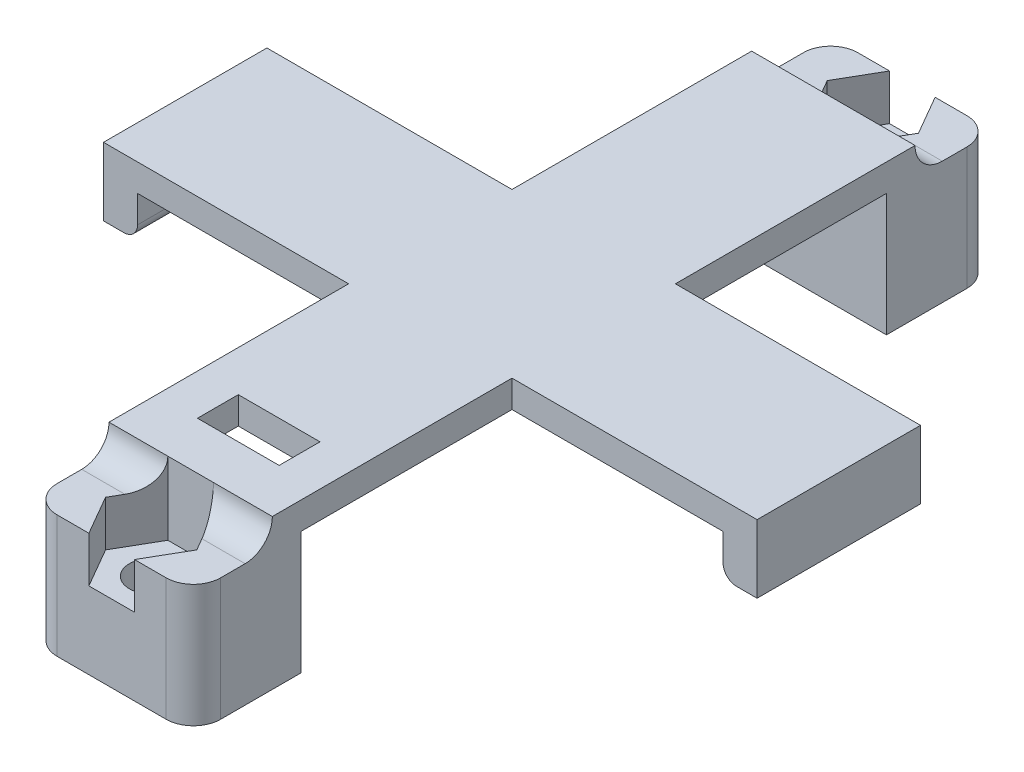
SolidWorks part; units mm, degrees
ref_plane "Alzado" through (0, 0, 0) normal (0, 0, 1) x (1, 0, 0)
ref_plane "Planta" through (0, 0, 0) normal (0, 1, 0) x (1, 0, 0)
ref_plane "Vista lateral" through (0, 0, 0) normal (1, 0, 0) x (0, 0, -1)
sketch "Croquis2" plane through (0, 0, 0) normal (0, 1, 0) x (1, 0, 0)
  line L0 (27.5, 15.5) -> (27.5, 0)
  line L1 (0, 0) -> (43, 0)
  line L2 (0, 0) -> (0, 43)
  line L3 (0, 43) -> (43, 43)
  line L4 (43, 0) -> (43, 43)
  line L5 (15.5, 43) -> (27.5, 43)
  line L6 (15.5, 43) -> (15.5, 27.5)
  line L7 (15.5, 0) -> (27.5, 0)
  line L8 (27.5, 43) -> (27.5, 27.5)
  line L9 (27.5, 27.5) -> (43, 27.5)
  line L11 (27.5, 15.5) -> (43, 15.5)
  line L12 (43, 27.5) -> (43, 15.5)
  line L13 (15.5, 27.5) -> (0, 27.5)
  line L15 (15.5, 15.5) -> (0, 15.5)
  line L16 (0, 27.5) -> (0, 15.5)
  line L17 (15.5, 15.5) -> (15.5, 0)
  dimension "D1" = 43
  dimension "D2" = 43
  dimension "D3" = 12
  dimension "D4" = 15.5
  dimension "D5" = 12
  dimension "D6" = 12
  dimension "D7" = 15.5
  dimension "D8" = 15.5
extrude "Saliente-Extruir1" add sketch "Croquis2" along normal blind 2 contours L15 L17 L1 L0 L11 L4 L9 L8 L3 L6 L13 L2 region at (21.5, 0, -21.5)
sketch "Croquis3" plane through (0, 0, 0) normal (0, -1, 0) x (1, 0, 0)
  line L1 (27.5, -43) -> (15.5, -43)
  line L2 (27.5, -43) -> (27.5, -50.9)
  line L3 (27.5, -50.9) -> (15.5, -50.9)
  line L4 (15.5, -43) -> (15.5, -50.9)
  line L5 (27.5, 0) -> (15.5, 0)
  line L6 (27.5, 0) -> (27.5, 7.9)
  line L7 (27.5, 7.9) -> (15.5, 7.9)
  line L8 (15.5, 0) -> (15.5, 7.9)
  dimension "D1" = 7.9
  dimension "D2" = 7.9
extrude "Saliente-Extruir2" add sketch "Croquis3" along normal blind 9 separate body
sketch "Croquis4" plane through (0, 0, 0) normal (0, 1, 0) x (1, 0, 0)
  line L0 (21.5, 50.9) -> (21.5, -7.9) construction
  line L1 (15.5, 50.9) -> (27.5, 50.9) construction
  line L2 (27.5, -7.9) -> (15.5, -7.9) construction
  line L3 (15.5, 0) -> (27.5, 0) construction
  line L4 (15.5, 43) -> (27.5, 43) construction
  circle A0 centre (21.5, 48) radius 1.6
  circle A1 centre (21.5, -5) radius 1.6
  dimension "D1" = 3.2
  dimension "D2" = 3.2
  dimension "D3" = 5
  dimension "D4" = 5
extrude "Cortar-Extruir1" cut sketch "Croquis4" against normal up to surface (9 mm away) up to face at (21.5, -9, -46.95)
sketch "Croquis7" plane through (0, 0, 0) normal (0, 1, 0) x (1, 0, 0)
  line L1 (24.8486, 48) -> (23.1743, 50.9)
  line L2 (23.1743, 50.9) -> (19.8257, 50.9)
  line L3 (19.8257, 50.9) -> (18.1514, 48)
  line L4 (18.1514, 48) -> (19.8257, 45.1)
  line L5 (19.8257, 45.1) -> (23.1743, 45.1)
  line L6 (23.1743, 45.1) -> (24.8486, 48)
  line L8 (15.5, 43) -> (27.5, 43) construction
  line L9 (15.5, 0) -> (27.5, 0) construction
  line L10 (24.8486, -5) -> (23.1743, -2.1)
  line L11 (23.1743, -2.1) -> (19.8257, -2.1)
  line L12 (19.8257, -2.1) -> (18.1514, -5)
  line L13 (18.1514, -5) -> (19.8257, -7.9)
  line L14 (19.8257, -7.9) -> (23.1743, -7.9)
  line L15 (23.1743, -7.9) -> (24.8486, -5)
  circle A0 centre (21.5, 48) radius 2.9 construction
  circle A1 centre (21.5, -5) radius 2.9 construction
  dimension "D1" = 5.8
  dimension "D2" = 5.8
extrude "Cortar-Extruir2" cut sketch "Croquis7" against normal blind 3.35
sketch "Croquis8" plane through (0, 0, 0) normal (0, 1, 0) x (1, 0, 0)
  line L0 (27.5, 50.9) -> (27.5, 43) construction
  line L1 (15.5, 43) -> (27.5, 43)
  line L2 (15.5, 43) -> (15.5, 45.1)
  line L3 (15.5, 45.1) -> (27.5, 45.1)
  line L4 (27.5, 43) -> (27.5, 45.1)
  line L5 (19.8257, 45.1) -> (23.1743, 45.1) construction
  line L6 (27.5, 0) -> (27.5, -7.9) construction
  line L7 (15.5, 0) -> (27.5, 0)
  line L8 (15.5, 0) -> (15.5, -2.1)
  line L9 (15.5, -2.1) -> (27.5, -2.1)
  line L10 (27.5, 0) -> (27.5, -2.1)
  line L11 (23.1743, -2.1) -> (19.8257, -2.1) construction
extrude "Saliente-Extruir3" add sketch "Croquis8" along normal up to surface (2 mm away) up to face at (21.5, 2, -21.5)
fillet "Redondeo1" radius 2 8 edges at (17.6628, 0, -45.1) (25.3372, 0, -45.1) (17.6628, 0, 2.1) (25.3372, 0, 2.1) (15.5, -4.5, 7.9) (27.5, -4.5, 7.9) (15.5, -4.5, -50.9) (27.5, -4.5, -50.9)
sketch "Croquis9" plane through (0, 2, 0) normal (0, 1, 0) x (1, 0, 0)
  line L1 (0, 27.5) -> (-2.5, 27.5)
  line L2 (0, 27.5) -> (0, 15.5)
  line L3 (0, 15.5) -> (-2.5, 15.5)
  line L4 (-2.5, 27.5) -> (-2.5, 15.5)
  line L5 (43, 27.5) -> (45.5, 27.5)
  line L6 (43, 27.5) -> (43, 15.5)
  line L7 (43, 15.5) -> (45.5, 15.5)
  line L8 (45.5, 27.5) -> (45.5, 15.5)
  dimension "D1" = 2.5
  dimension "D2" = 2.5
extrude "Saliente-Extruir4" add sketch "Croquis9" against normal blind 5
fillet "Redondeo2" radius 1 2 edges at (0, -3, -21.5) (43, -3, -21.5)
sketch "Croquis10" plane through (0, 2, 0) normal (0, 1, 0) x (1, 0, 0)
  line L1 (24.5, 1.4) -> (18.5, 1.4)
  line L2 (24.5, 1.4) -> (24.5, 4.4)
  line L3 (24.5, 4.4) -> (18.5, 4.4)
  line L4 (18.5, 1.4) -> (18.5, 4.4)
  line L5 (27.5, 15.5) -> (27.5, -2.1) construction
  line L6 (15.5, -2.1) -> (19.8257, -2.1) construction
  dimension "D1" = 6
  dimension "D2" = 3
  dimension "D3" = 3
  dimension "D4" = 3.5
extrude "Cortar-Extruir3" cut sketch "Croquis10" against normal blind 8
